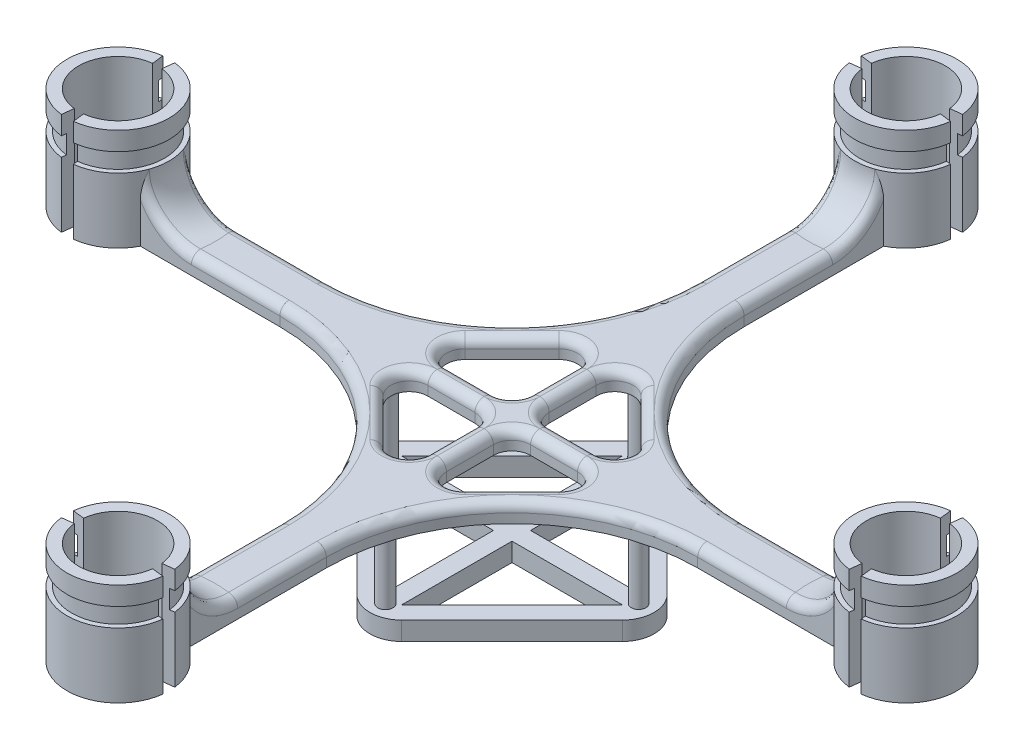
SolidWorks part; units mm, degrees
note: The reader was unsure of these and kept them because the rebuilt part matched: shared geometry of "Sketch1<4>", "Sketch1<6>", "Sketch3<4>".
material "ABS"
ref_plane "Front Plane" through (0, 0, 0) normal (0, 0, 1) x (1, 0, 0)
ref_plane "Top Plane" through (0, 0, 0) normal (0, 1, 0) x (1, 0, 0)
ref_plane "Right Plane" through (0, 0, 0) normal (1, 0, 0) x (0, 0, -1)
sketch "Sketch1" plane through (0, 0, 0) normal (0, 1, 0) x (1, 0, 0)
  line L0 (-42.4264, 0) -> (42.4264, 0) construction
  line L1 (0, -42.4264) -> (0, 42.4264) construction
  line L2 (-42.4264, 2.5) -> (-42.4264, 0) construction
  line L7 (-42.4264, 0) -> (-42.4264, -2.5) construction
  line L8 (42.4264, 0) -> (42.4264, -2.5) construction
  line L9 (-2.5, 42.4264) -> (0, 42.4264) construction
  line L10 (0, 42.4264) -> (2.5, 42.4264) construction
  line L11 (42.4264, 2.5) -> (42.4264, 0) construction
  line L12 (-42.9264, -4.2205) -> (-43.0735, -5.4618)
  line L13 (-41.9264, -4.2205) -> (-41.7793, -5.4618)
  line L14 (-42.9264, 4.2205) -> (-43.0735, 5.4618)
  line L15 (-41.9264, 4.2205) -> (-41.7793, 5.4618)
  line L16 (41.9264, -4.2205) -> (41.7793, -5.4618)
  line L17 (42.9264, -4.2205) -> (43.0735, -5.4618)
  line L18 (41.9264, 4.2205) -> (41.7793, 5.4618)
  line L19 (42.9264, 4.2205) -> (43.0735, 5.4618)
  line L20 (-4.2205, 41.9264) -> (-5.4618, 41.7793)
  line L21 (-4.2205, 42.9264) -> (-5.4618, 43.0735)
  line L22 (4.2205, 41.9264) -> (5.4618, 41.7793)
  line L23 (4.2205, 42.9264) -> (5.4618, 43.0735)
  line L24 (4.2205, -42.9264) -> (5.4618, -43.0735)
  line L25 (4.2205, -41.9264) -> (5.4618, -41.7793)
  line L26 (-4.2205, -41.9264) -> (-5.4618, -41.7793)
  line L27 (-4.2205, -42.9264) -> (-5.4618, -43.0735)
  line L28 (2.5, -42.4264) -> (0, -42.4264) construction
  line L29 (0, -42.4264) -> (-2.5, -42.4264) construction
  line L30 (-55, 0) -> (55, 0) construction
  line L31 (0, -55) -> (0, 55) construction
  line L33 (-42.4264, 2.5) -> (42.4264, 2.5)
  line L34 (-42.4264, 2.5) -> (-42.4264, -2.5)
  line L35 (-42.4264, -2.5) -> (42.4264, -2.5)
  line L36 (42.4264, 2.5) -> (42.4264, -2.5)
  line L37 (-2.5, 42.4264) -> (2.5, 42.4264)
  line L38 (-2.5, 42.4264) -> (-2.5, -42.4264)
  line L39 (-2.5, -42.4264) -> (2.5, -42.4264)
  line L40 (2.5, 42.4264) -> (2.5, -42.4264)
  circle A0 centre (-42.4264, 0) radius 4.25
  circle A1 centre (0, 42.4264) radius 4.25
  circle A2 centre (42.4264, 0) radius 4.25
  circle A3 centre (0, -42.4264) radius 4.25
  circle A4 centre (-42.4264, 0) radius 5.5
  circle A5 centre (0, -42.4264) radius 5.5
  circle A6 centre (42.4264, 0) radius 5.5
  circle A7 centre (0, 42.4264) radius 5.5
  circle A9 centre (-42.4264, 2.5) radius 0.5
  circle A10 centre (-42.4264, -2.5) radius 0.5
  circle A11 centre (42.4264, -2.5) radius 0.5
  circle A12 centre (42.4264, 2.5) radius 0.5
  circle A13 centre (2.5, 42.4264) radius 0.5
  circle A14 centre (-2.5, 42.4264) radius 0.5
  circle A15 centre (2.5, -42.4264) radius 0.5
  circle A16 centre (-2.5, -42.4264) radius 0.5
  circle A17 centre (0, -42.4264) radius 5
  circle A18 centre (0, 42.4264) radius 5
  circle A19 centre (-42.4264, 0) radius 5
  circle A20 centre (42.4264, 0) radius 5
  dimension "D5" = 10
  dimension "D6" = 10
  dimension "D4" = 2.5
  dimension "D2" = 8.5
  dimension "D3" = 11
  dimension "D1" = 60
extrude "Boss-Extrude1" add sketch "Sketch1" along normal blind 2 contours A14 L37 A13 L40 A1 L38 | A18 L21 A1 L23 | L21 A18 L23 A7 | A18 L38 A1 L20 | L38 A18 L20 A7 | A14 L38 A1 L40 A13 L37 | A18 L40 A1 L38 | A7 L38 L33 L40 | A18 L22 A1 L40 | L22 A18 L40 A7 | L40 A18 L38 A7 | A6 L33 L40 L35 | L36 A12 L33 A2 L35 A11 | L33 A12 L36 A11 L35 A2 | A20 L19 A2 L17 | L19 A20 L17 A6 | A20 L16 A2 L35 | L16 A20 L35 A6 | A20 L35 A2 L33 | L35 A20 L33 A6 | A20 L33 A2 L18 | L33 A20 L18 A6 | A5 L40 L35 L38 | L39 A16 L38 A3 L40 A15 | L38 A16 L39 A15 L40 A3 | L27 A17 L24 A3 | A17 L27 A5 L24 | L38 A17 L26 A3 | A17 L38 A5 L26 | L40 A17 L38 A3 | L25 A17 L40 A3 | A17 L25 A5 L40 | A17 L40 A5 L38 | A4 L35 L38 L33 | A10 L35 A0 L33 A9 L34 | A10 L34 A9 L33 A0 L35 | L14 A19 L12 A0 | A19 L14 A4 L12 | L33 A19 L15 A0 | A19 L33 A4 L15 | A19 L35 A4 L33 | A19 L13 A4 L35 | L13 A19 L35 A0 | L35 A19 L33 A0 | L40 L33 L38 L35
extrude "Boss-Extrude2" add sketch "Sketch1<4>" along normal blind 11 contours L14 A19 L12 A0 | A19 L14 A4 L12 | L13 A19 L15 A0 | A19 L13 A4 L15 | A17 L27 A5 L24 | L27 A17 L24 A3 | L25 A17 L26 A3 | A17 L25 A5 L26 | A20 L16 A2 L18 | L16 A20 L18 A6 | A20 L19 A2 L17 | L19 A20 L17 A6 | L22 A18 L20 A7 | A18 L22 A1 L20 | A18 L21 A1 L23 | L21 A18 L23 A7 | L13 A19 L35 A0 | A19 L13 A4 L35 | L33 A19 L15 A0 | A19 L33 A4 L15 | A18 L38 A1 L20 | L38 A18 L20 A7 | A18 L22 A1 L40 | L22 A18 L40 A7 | L16 A20 L35 A6 | A20 L16 A2 L35 | A20 L33 A2 L18 | L33 A20 L18 A6 | L38 A17 L26 A3 | A17 L38 A5 L26 | A17 L25 A5 L40 | L25 A17 L40 A3
sketch "Sketch1<4>" plane through (0, 0, 0) normal (0, 1, 0) x (1, 0, 0) same geometry as "Sketch1"
extrude "Cut-Extrude1" cut sketch "Sketch1<6>" along normal blind 2 from offset 7 contours L19 A20 L17 A6 | L16 A20 L18 A6 | L21 A18 L23 A7 | L22 A18 L20 A7 | A19 L14 A4 L12 | A19 L13 A4 L15 | A17 L25 A5 L26 | A17 L27 A5 L24 | A19 L13 A4 L35 | A19 L33 A4 L15 | A17 L38 A5 L26 | A17 L25 A5 L40 | L16 A20 L35 A6 | L33 A20 L18 A6 | L22 A18 L40 A7 | L38 A18 L20 A7
sketch "Sketch1<6>" plane through (0, 0, 0) normal (0, 1, 0) x (1, 0, 0) same geometry as "Sketch1"
fillet "Fillet1" radius 20 4 edges at (-2.5, 1, -2.5) (-2.5, 1, 2.5) (2.5, 1, 2.5) (2.5, 1, -2.5)
sketch "Sketch2" plane through (0, 2, 0) normal (0, 1, 0) x (1, 0, 0)
  line L0 (-1, -12.8873) -> (-12.8873, -1)
  line L1 (1, -12.8873) -> (12.8873, -1)
  line L2 (-12.8873, 1) -> (-1, 12.8873)
  line L3 (12.8873, 1) -> (1, 12.8873)
  line L4 (-1, -1) -> (1, 1) construction
  line L5 (1, -1) -> (-1, 1) construction
  line L6 (-12.8873, -1) -> (-1, -1)
  line L7 (1, -12.8873) -> (1, -1)
  line L12 (-12.8873, 1) -> (-1, 1)
  line L13 (-1, -12.8873) -> (-1, -1)
  line L20 (1, 1) -> (12.8873, 1)
  line L24 (1, -1) -> (12.8873, -1)
  line L27 (-1, 1) -> (-1, 12.8873)
  line L29 (1, 1) -> (1, 12.8873)
  circle A0 centre (-13.6373, 0) radius 1
  arc A1 (2.5, 22.5) -> (22.5, 2.5) centre (22.5, 22.5) ccw construction
  circle A2 centre (0, 13.6373) radius 1
  circle A3 centre (13.6373, 0) radius 1
  circle A4 centre (0, -13.6373) radius 1
  point P1 (0, 0)
  point P6 (0, 0)
  point P22 (0, 0)
  point P23 (0, 0)
  point P24 (0, 0)
  dimension "D1" = 22
  dimension "D2" = 2
  dimension "D3" = 1.25
  dimension "D4" = 1.25
  dimension "D5" = 1.25
  dimension "D6" = 1.25
extrude "Cut-Extrude2" cut sketch "Sketch2" against normal up to next contours L0 L13 L6 | L24 L7 L1 | L29 L20 L3 | L12 L27 L2
fillet "Fillet2" radius 2 12 edges at (-1, 1, 12.8873) (1, 1, 12.8873) (12.8873, 1, 1) (-12.8873, 1, 1) (-12.8873, 1, -1) (12.8873, 1, -1) (-1, 1, -12.8873) (1, 1, -12.8873) (1, 1, -1) (-1, 1, -1) (-1, 1, 1) (1, 1, 1)
fillet "Fillet6" radius 5 4 edges at (0, 2, 36.9264) (36.9264, 2, 0) (0, 2, -36.9264) (-36.9264, 2, 0)
fillet "Fillet5" radius 1 44 edges at (-27.3642, 2, 2.5) (2.5, 2, -27.3642) (-2.5, 2, -27.3642) (-27.3642, 2, -2.5) (-35.6024, 3.1854, 2.5) (-36.4889, 4.0784, -2.5) (-2.5, 3.1854, -35.6024) (2.5, 4.0784, -36.4889) (2.5, 3.1854, 35.6024) (-2.5, 4.0784, 36.4889) (35.6024, 3.1854, -2.5) (36.4889, 4.0784, 2.5) (-2.5, 2, 27.3642) (27.3642, 2, 2.5) (2.5, 2, 27.3642) (27.3642, 2, -2.5) (-8.3579, 2, 8.3579) (8.3579, 2, 8.3579) (8.3579, 2, -8.3579) (-8.3579, 2, -8.3579) (-1, 2, 5.5294) (-6.9437, 2, 6.9437) (6.9437, 2, 6.9437) (1, 2, 5.5294) (5.5294, 2, 1) (-5.5294, 2, 1) (-5.5294, 2, -1) (-6.9437, 2, -6.9437) (6.9437, 2, -6.9437) (5.5294, 2, -1) (-1, 2, -5.5294) (1, 2, -5.5294) (-2.2346, 2, 9.9066) (2.2346, 2, 9.9066) (9.9066, 2, 2.2346) (-9.9066, 2, 2.2346) (-9.9066, 2, -2.2346) (9.9066, 2, -2.2346) (-2.2346, 2, -9.9066) (2.2346, 2, -9.9066) (1.5858, 2, -1.5858) (-1.5858, 2, -1.5858) (-1.5858, 2, 1.5858) (1.5858, 2, 1.5858)
ref_plane "Plane1" through (0, -10, 0) normal (0, -1, 0) x (-1, 0, 0)
sketch "Sketch3" plane through (0, -10, 0) normal (0, -1, 0) x (-1, 0, 0)
  line L4 (-2.4142, 14.3015) -> (-14.3015, 2.4142)
  line L5 (14.3015, 2.4142) -> (2.4142, 14.3015)
  line L6 (2.4142, -14.3015) -> (14.3015, -2.4142)
  line L7 (-1, 1) -> (-1, 12.8873)
  line L8 (-1, 12.8873) -> (-12.8873, 1)
  line L9 (-12.8873, 1) -> (-1, 1)
  line L10 (-1, 1) -> (-1, 12.8873)
  line L11 (-1, 12.8873) -> (-12.8873, 1)
  line L12 (-12.8873, 1) -> (-1, 1)
  line L13 (1, 12.8873) -> (1, 1)
  line L14 (12.8873, 1) -> (1, 12.8873)
  line L15 (1, 1) -> (12.8873, 1)
  line L16 (1, 12.8873) -> (1, 1)
  line L17 (12.8873, 1) -> (1, 12.8873)
  line L18 (1, 1) -> (12.8873, 1)
  line L19 (-1, -1) -> (-12.8873, -1)
  line L20 (-12.8873, -1) -> (-1, -12.8873)
  line L21 (-1, -12.8873) -> (-1, -1)
  line L22 (-1, -1) -> (-12.8873, -1)
  line L23 (-12.8873, -1) -> (-1, -12.8873)
  line L24 (-1, -12.8873) -> (-1, -1)
  line L25 (12.8873, -1) -> (1, -1)
  line L26 (1, -12.8873) -> (12.8873, -1)
  line L27 (1, -1) -> (1, -12.8873)
  line L28 (12.8873, -1) -> (1, -1)
  line L29 (1, -12.8873) -> (12.8873, -1)
  line L30 (1, -1) -> (1, -12.8873)
  line L31 (-14.3015, -2.4142) -> (-2.4142, -14.3015)
  arc A0 (-2.4142, 14.3015) -> (2.4142, 14.3015) centre (0, 11.8873) cw
  arc A1 (14.3015, 2.4142) -> (14.3015, -2.4142) centre (11.8873, 0) cw
  arc A2 (-2.4142, -14.3015) -> (2.4142, -14.3015) centre (0, -11.8873) ccw
  arc A3 (-14.3015, 2.4142) -> (-14.3015, -2.4142) centre (-11.8873, 0) ccw
  circle A4 centre (-13.6373, 0) radius 0.7862
  circle A5 centre (0, 13.6373) radius 0.8277
  circle A6 centre (13.6373, 0) radius 1
  circle A7 centre (0, -13.6373) radius 0.8121
  point P33 (0, 0)
  point P34 (0, 0)
  dimension "D5" = 1
  dimension "D6" = 1
  dimension "D7" = 1.75
  dimension "D8" = 1.75
  dimension "D9" = 1.75
  dimension "D10" = 1.75
  dimension "D1" = 0
  dimension "D2" = 0
  dimension "D3" = 0
  dimension "D4" = 0
extrude "Boss-Extrude3" add sketch "Sketch3" along normal mid plane 2 separate body contours L4 A3 L31 A2 L6 A1 L5 A0 A7 A6 A5 A4 L12 L11 L10 L18 L16 L17 L24 L23 L22 L30 L28 L29 | A5 | A4 | A6 | A7
extrude "Boss-Extrude4" add sketch "Sketch3<4>" against normal up to surface (10 mm away) contours A4 | A5 | A6 | A7
sketch "Sketch3<4>" plane through (0, -10, 0) normal (0, -1, 0) x (-1, 0, 0) same geometry as "Sketch3"
